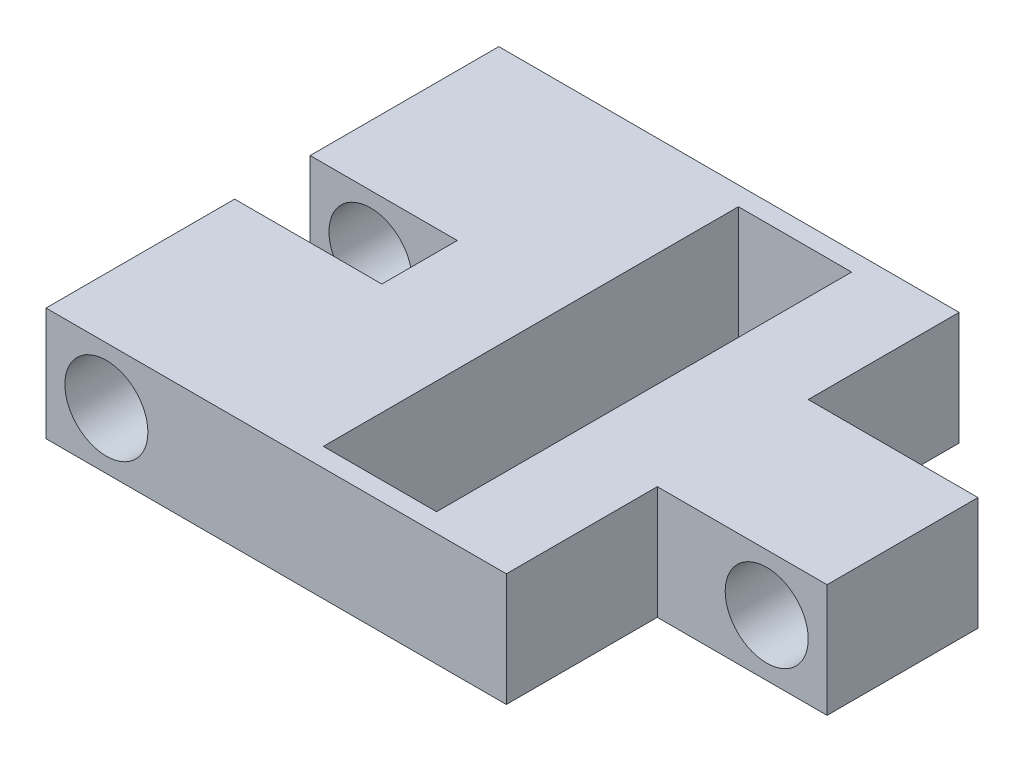
SolidWorks part; units mm, degrees
ref_plane "Front Plane" through (0, 0, 0) normal (0, 0, 1) x (1, 0, 0)
ref_plane "Top Plane" through (0, 0, 0) normal (0, 1, 0) x (1, 0, 0)
ref_plane "Right Plane" through (0, 0, 0) normal (1, 0, 0) x (0, 0, -1)
sketch "Sketch1" plane through (0, 0, 0) normal (0, 0, 1) x (1, 0, 0)
  line L0 (0, 0) -> (-8.35, 0) construction
  line L1 (-8.35, -1.5) -> (8.35, -1.5)
  line L2 (-8.35, -1.5) -> (-8.35, 1.5)
  line L3 (-8.35, 1.5) -> (8.35, 1.5)
  line L4 (8.35, -1.5) -> (8.35, 1.5)
  line L5 (-8.35, -1.5) -> (8.35, 1.5) construction
  line L6 (-8.35, 1.5) -> (8.35, -1.5) construction
  line L7 (0, 0) -> (8.35, 0) construction
  circle A0 centre (-6.75, 0) radius 1.1
  circle A1 centre (6.75, 0) radius 1.1
  point P1 (0, 0)
  dimension "D3" = 2.2
  dimension "D4" = 2.2
  dimension "D1" = 16.7
  dimension "D2" = 3
  dimension "D5" = 13.5
  dimension "D6" = 1.6
extrude "Boss-Extrude1" add sketch "Sketch1" along normal blind 6 and the other way blind 6
sketch "Sketch2" plane through (0, 1.5, 0) normal (0, 1, 0) x (1, 0, 0)
  line L0 (-8.35, 6) -> (-8.35, -6) construction
  line L1 (-1.5, -5.5) -> (1.5, -5.5)
  line L2 (-1.5, -5.5) -> (-1.5, 5.5)
  line L3 (-1.5, 5.5) -> (1.5, 5.5)
  line L4 (1.5, -5.5) -> (1.5, 5.5)
  line L5 (-1.5, -5.5) -> (1.5, 5.5) construction
  line L6 (-1.5, 5.5) -> (1.5, -5.5) construction
  line L7 (12.85, -10) -> (3.85, -10)
  line L8 (12.85, -10) -> (12.85, -2)
  line L9 (12.85, -2) -> (3.85, -2)
  line L10 (3.85, -10) -> (3.85, -2)
  line L11 (12.85, -10) -> (3.85, -2) construction
  line L12 (12.85, -2) -> (3.85, -10) construction
  line L13 (12.85, 10) -> (3.85, 10)
  line L14 (12.85, 10) -> (12.85, 2)
  line L15 (12.85, 2) -> (3.85, 2)
  line L16 (3.85, 10) -> (3.85, 2)
  line L17 (12.85, 10) -> (3.85, 2) construction
  line L18 (12.85, 2) -> (3.85, 10) construction
  line L19 (-12.25, -1) -> (-4.45, -1)
  line L20 (-12.25, -1) -> (-12.25, 1)
  line L21 (-12.25, 1) -> (-4.45, 1)
  line L22 (-4.45, -1) -> (-4.45, 1)
  line L23 (-12.25, -1) -> (-4.45, 1) construction
  line L24 (-12.25, 1) -> (-4.45, -1) construction
  point P0 (0, 0)
  point P5 (8.35, -6)
  point P11 (8.35, 6)
  point P17 (-8.35, 0)
  dimension "D1" = 3
  dimension "D2" = 11
  dimension "D3" = 4
  dimension "D4" = 9
  dimension "D5" = 9
  dimension "D6" = 8
  dimension "D7" = 2
  dimension "D8" = 7.8
extrude "Cut-Extrude1" cut sketch "Sketch2" against normal blind 5
